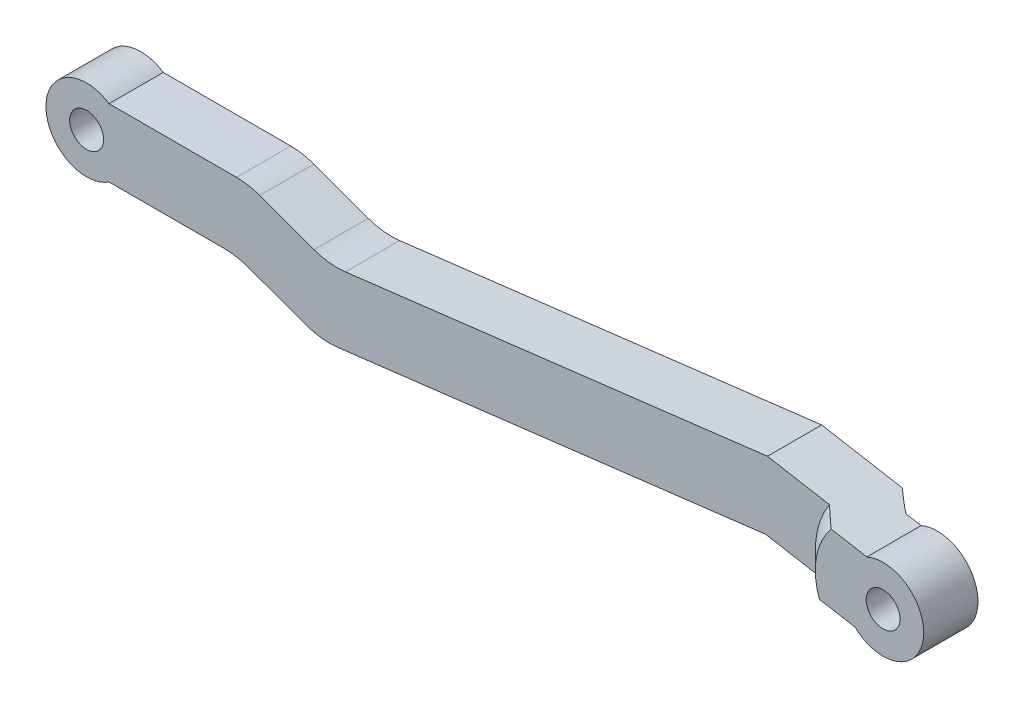
SolidWorks part; units mm, degrees
material "Vero PureWhite"
ref_plane "前视基准面" through (0, 0, 0) normal (0, 0, 1) x (1, 0, 0)
ref_plane "上视基准面" through (0, 0, 0) normal (0, 1, 0) x (1, 0, 0)
ref_plane "右视基准面" through (0, 0, 0) normal (1, 0, 0) x (0, 0, -1)
other "Configuration Table"
sketch "草图1" plane through (0, 0, 0) normal (0, 0, 1) x (1, 0, 0)
  line L0 (0, 0) -> (-120, 0) construction
  line L3 (0, 0) -> (-19.6962, 3.473) construction
  line L4 (-19.6962, 3.473) -> (-84.784, -4.4463) construction
  line L5 (-84.784, -4.4463) -> (-97, 0) construction
  line L6 (-97, 0) -> (-120, 0) construction
  line L7 (-2.398, 5.5) -> (-19.5611, 8.5263)
  line L8 (-19.5611, 8.5263) -> (-84.1992, 0.6618)
  line L9 (-84.1992, 0.6618) -> (-96.1184, 5)
  line L10 (-96.1184, 5) -> (-116.6834, 5)
  line L11 (-4.1345, -4.3481) -> (-19.8313, -1.5803)
  line L12 (-19.8313, -1.5803) -> (-85.3688, -9.5543)
  line L13 (-85.3688, -9.5543) -> (-97.8816, -5)
  line L14 (-97.8816, -5) -> (-116.6834, -5)
  line L15 (0.8682, 4.924) -> (-19.5611, 8.5263) construction
  line L16 (-0.8682, -4.924) -> (-19.8313, -1.5803) construction
  line L17 (-96.1184, 5) -> (-120, 5) construction
  line L18 (-97.8816, -5) -> (-120, -5) construction
  arc A0 (-4.1345, -4.3481) -> (-2.398, 5.5) centre (0, 0) ccw
  arc A1 (-116.6834, 5) -> (-116.6834, -5) centre (-120, 0) ccw
  arc A2 (-0.7041, 5.9585) -> (1.0949, -5.8993) centre (0, 0) ccw construction
  point P3 (-60, 0)
  dimension "D2" = 20
  dimension "D1" = 120
  dimension "D3" = 23
  dimension "D4" = 13
  dimension "D5" = 20
  dimension "D6" = 10
  dimension "D7" = 5
  dimension "D8" = 5
extrude "凸台-拉伸1" add sketch "草图1" along normal mid plane 8
sketch "草图2" plane through (0, 0, -4) normal (0, 0, -1) x (-1, 0, 0)
  circle A0 centre (0, 0) radius 10
  dimension "D1" = 20
extrude "切除-拉伸1" cut sketch "草图2" against normal blind 2.5
sketch "草图3" plane through (0, 0, 4) normal (0, 0, 1) x (1, 0, 0)
  line L2 (-2.398, 5.5) -> (-7.6604, 6.4279)
  line L3 (-9.3969, -3.4202) -> (-4.1345, -4.3481)
  line L4 (-2.398, 5.5) -> (-7.6604, 6.4279)
  line L5 (-9.3969, -3.4202) -> (-4.1345, -4.3481)
  arc A2 (-4.1345, -4.3481) -> (-2.398, 5.5) centre (0, 0) ccw
  arc A3 (-7.6604, 6.4279) -> (-9.3969, -3.4202) centre (0, 0) ccw
  arc A4 (-4.1345, -4.3481) -> (-2.398, 5.5) centre (0, 0) ccw
  arc A5 (-7.6604, 6.4279) -> (-9.3969, -3.4202) centre (0, 0) ccw
  dimension "D1" = 0
extrude "凸台-拉伸4" add sketch "草图3" along normal offset from surface (2.5 mm away) 8 up to face at (-3.9335, 0.6936, -1.5)
sketch "草图4" plane through (0, 0, -1.5) normal (0, 0, -1) x (-1, 0, 0)
  circle A2 centre (0, 0) radius 2.5
  circle A3 centre (120, 0) radius 2.5003
  dimension "D1" = 5
  dimension "D2" = 5.0006
extrude "切除-拉伸2" cut sketch "草图4" against normal through all both and the other way through all
chamfer "倒角1" distance 2.5 angle 45 1 edges at (-9.8481, 1.7365, 4)
chamfer "倒角2" distance 2.5 angle 45 1 edges at (-9.8481, 1.7365, -1.5)
fillet "圆角1" radius 10 4 edges at (-85.3688, -9.5543, 0) (-97.8816, -5, 0) (-84.1992, 0.6618, 0) (-96.1184, 5, 0)
